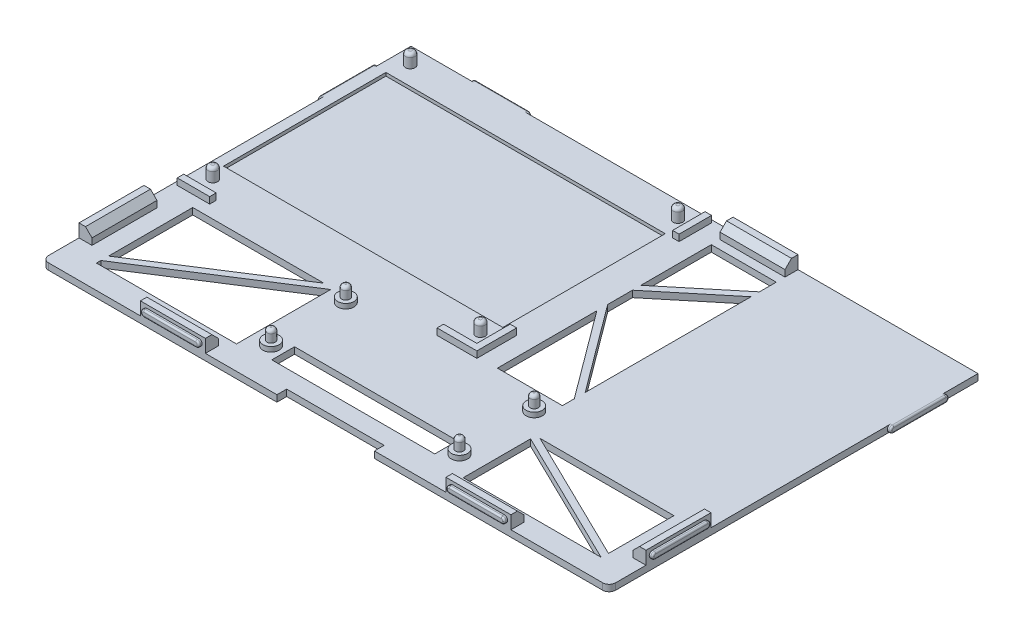
SolidWorks part; units mm, degrees
ref_plane "前基準面" through (0, 0, 0) normal (0, 0, 1) x (1, 0, 0)
ref_plane "上基準面" through (0, 0, 0) normal (0, 1, 0) x (1, 0, 0)
ref_plane "右基準面" through (0, 0, 0) normal (1, 0, 0) x (0, 0, -1)
sketch "草圖1" plane through (0, 0, 0) normal (0, 1, 0) x (1, 0, 0)
  line L0 (0, 56.775) -> (0, -56.775) construction
  line L1 (-87.275, 56.775) -> (87.275, 56.775)
  line L2 (-87.275, 56.775) -> (-87.275, -56.775)
  line L3 (-87.275, -56.775) -> (87.275, -56.775)
  line L4 (87.275, 56.775) -> (87.275, -56.775)
  line L5 (-87.275, 56.775) -> (87.275, -56.775) construction
  line L6 (-87.275, -56.775) -> (87.275, 56.775) construction
  line L7 (-87.275, 0) -> (87.275, 0) construction
  point P0 (0, 0)
  dimension "D1" = 174.55
  dimension "D2" = 113.55
extrude "填料-伸長1" add sketch "草圖1" along normal blind 2
sketch "草圖2" plane through (0, 2, 0) normal (0, 1, 0) x (1, 0, 0)
  line L1 (-86.16, 55.93) -> (3.84, 55.93)
  line L2 (-86.16, 55.93) -> (-86.16, -14.07)
  line L3 (-86.16, -14.07) -> (3.84, -14.07)
  line L4 (3.84, 55.93) -> (3.84, -14.07)
  line L5 (-86.16, 55.93) -> (3.84, -14.07) construction
  line L6 (-86.16, -14.07) -> (3.84, 55.93) construction
  line L8 (-41.16, 55.93) -> (-41.16, -14.07) construction
  line L9 (-86.16, 20.93) -> (3.84, 20.93) construction
  line L10 (0, 56.775) -> (0, -56.775) construction
  line L11 (-87.275, 0) -> (87.275, 0) construction
  point P0 (-41.16, 20.93)
  dimension "D1" = 90
  dimension "D2" = 70
  dimension "D3" = 41.16
  dimension "D4" = 20.93
sketch "草圖3" plane through (0, 2, 0) normal (0, 1, 0) x (1, 0, 0)
  line L0 (3.84, 55.93) -> (3.84, -14.07) construction
  line L1 (4.09, 55.93) -> (6.09, 55.93)
  line L2 (4.09, 55.93) -> (4.09, 45.93)
  line L3 (4.09, 45.93) -> (6.09, 45.93)
  line L4 (6.09, 55.93) -> (6.09, 45.93)
  line L5 (-86.16, -14.07) -> (3.84, -14.07) construction
  line L7 (4.09, -14.07) -> (4.09, -4.07)
  line L8 (4.09, -4.07) -> (6.09, -4.07)
  line L9 (6.09, -14.07) -> (6.09, -4.07)
  line L10 (6.09, -16.32) -> (-6.16, -16.32)
  line L11 (6.09, -16.32) -> (6.09, -15.07)
  line L12 (4.09, -14.32) -> (-6.16, -14.32)
  line L13 (-6.16, -16.32) -> (-6.16, -14.32)
  line L14 (3.84, -14.32) -> (3.84, -16.32) construction
  line L15 (4.09, -14.07) -> (4.09, -14.32)
  line L16 (6.09, -14.07) -> (6.09, -15.07)
  line L18 (-86.16, -16.32) -> (-76.16, -16.32)
  line L19 (-86.16, -16.32) -> (-86.16, -14.32)
  line L20 (-86.16, -14.32) -> (-76.16, -14.32)
  line L21 (-76.16, -16.32) -> (-76.16, -14.32)
  dimension "D1" = 2
  dimension "D2" = 10
  dimension "D3" = 0.25
  dimension "D4" = 2
  dimension "D5" = 2
  dimension "D6" = 2
  dimension "D8" = 0.25
  dimension "D9" = 10
  dimension "D11" = 10
extrude "填料-伸長2" add sketch "草圖3" along normal blind 2
sketch "草圖4" plane through (0, 2, 0) normal (0, 1, 0) x (1, 0, 0)
  line L1 (-86.16, 55.93) -> (3.84, 55.93) construction
  line L2 (3.84, 55.93) -> (3.84, -14.07) construction
  line L3 (-86.16, -14.07) -> (3.84, -14.07) construction
  line L4 (-41.16, 55.93) -> (-41.16, -14.07) construction
  circle A0 centre (0.04, 51.63) radius 1.45
  circle A1 centre (0.04, -9.17) radius 1.45
  circle A2 centre (-82.36, -9.17) radius 1.45
  circle A3 centre (-82.36, 51.63) radius 1.45
  dimension "D1" = 2.9
  dimension "D2" = 3.8
  dimension "D3" = 4.3
  dimension "D4" = 4.9
extrude "填料-伸長3" add sketch "草圖4" along normal blind 4
fillet "圓角2" radius 1 4 edges at (-82.36, 6, -53.08) (-82.36, 6, 7.72) (0.04, 6, 10.62) (0.04, 6, -50.18)
sketch "草圖6" plane through (0, 2, 0) normal (0, 1, 0) x (1, 0, 0)
  line L1 (35.1797, 56.0179) -> (85.1797, 56.0179)
  line L2 (35.1797, 56.0179) -> (35.1797, -24.9821)
  line L3 (35.1797, -24.9821) -> (85.1797, -24.9821)
  line L4 (85.1797, 56.0179) -> (85.1797, -24.9821)
  line L5 (35.1797, 56.0179) -> (85.1797, -24.9821) construction
  line L6 (35.1797, -24.9821) -> (85.1797, 56.0179) construction
  point P0 (60.1797, 15.5179)
  dimension "D1" = 81
  dimension "D2" = 50
sketch "草圖5" plane through (0, 2, 0) normal (0, 1, 0) x (1, 0, 0)
  line L0 (-86.16, 55.93) -> (3.84, -14.07) construction
  line L1 (-84.16, 45.93) -> (1.84, 45.93)
  line L2 (-84.16, 45.93) -> (-84.16, -4.07)
  line L3 (-84.16, -4.07) -> (1.84, -4.07)
  line L4 (1.84, 45.93) -> (1.84, -4.07)
  line L5 (-84.16, 45.93) -> (1.84, -4.07) construction
  line L6 (-84.16, -4.07) -> (1.84, 45.93) construction
  line L7 (-86.16, 55.93) -> (3.84, 55.93) construction
  line L8 (-86.16, 55.93) -> (-86.16, -14.07) construction
  point P0 (-41.16, 20.93)
  dimension "D1" = 10
  dimension "D2" = 2
extrude "除料-伸長1" cut sketch "草圖5" against normal blind 1
sketch "草圖7" plane through (0, 2, 0) normal (0, 1, 0) x (1, 0, 0)
  line L0 (0, 56.775) -> (0, -56.775) construction
  line L1 (-32.5, -18.075) -> (32.5, -18.075)
  line L2 (-32.5, -18.075) -> (-32.5, -48.275)
  line L3 (-32.5, -48.275) -> (32.5, -48.275)
  line L4 (32.5, -18.075) -> (32.5, -48.275)
  line L5 (-32.5, -18.075) -> (32.5, -48.275) construction
  line L6 (-32.5, -48.275) -> (32.5, -18.075) construction
  line L7 (-87.275, -56.775) -> (87.275, -56.775) construction
  point P0 (0, -33.175)
  point P5 (32.5, -33.175)
  dimension "D1" = 65
  dimension "D2" = 30.2
  dimension "D3" = 8.5
sketch "草圖8" plane through (0, 2, 0) normal (0, 1, 0) x (1, 0, 0)
  line L0 (-32.5, -18.075) -> (32.5, -18.075) construction
  line L1 (32.5, -18.075) -> (32.5, -48.275) construction
  line L2 (-32.5, -48.275) -> (32.5, -48.275) construction
  line L3 (0, -18.075) -> (0, -48.275) construction
  circle A0 centre (29, -21.575) radius 2.5
  circle A1 centre (29, -21.575) radius 1.25
  circle A2 centre (29, -44.575) radius 2.5
  circle A3 centre (29, -44.575) radius 1.25
  circle A4 centre (-29, -44.575) radius 1.25
  circle A5 centre (-29, -44.575) radius 2.5
  circle A6 centre (-29, -21.575) radius 1.25
  circle A7 centre (-29, -21.575) radius 2.5
  dimension "D1" = 5
  dimension "D4" = 2.5
  dimension "D2" = 3.5
  dimension "D3" = 3.5
  dimension "D5" = 3.7
extrude "填料-伸長4" add sketch "草圖8" along normal blind 1.5 contours A6 | A7 A6 | A5 A4 | A4 | A0 A1 | A1 | A2 A3 | A3 region at (26.5707, 2, 21.575) region at (29, 2, 21.575) region at (26.5707, 2, 44.575) region at (29, 2, 44.575) region at (-29, 2, 44.575) region at (-31.4293, 2, 44.575) region at (-29, 2, 21.575) region at (-31.4293, 2, 21.575)
extrude "填料-伸長5" add sketch "草圖8<3>" along normal blind 5 contours A6 | A4 | A3 | A1 region at (29, 2, 21.575) region at (29, 2, 44.575) region at (-29, 2, 44.575) region at (-29, 2, 21.575)
sketch "草圖8<3>" plane through (0, 2, 0) normal (0, 1, 0) x (1, 0, 0) same geometry as "草圖8"
fillet "圓角3" radius 1 4 edges at (-29, 7, 45.825) (29, 7, 45.825) (29, 7, 22.825) (-29, 7, 22.825)
sketch "草圖9" plane through (0, 2, 0) normal (0, 1, 0) x (1, 0, 0)
  line L0 (0, 56.775) -> (0, -56.775) construction
  line L1 (-25.0798, -41.275) -> (25.0798, -41.275)
  line L2 (-25.0798, -41.275) -> (-25.0798, -48.275)
  line L3 (-25.0798, -48.275) -> (25.0798, -48.275)
  line L4 (25.0798, -41.275) -> (25.0798, -48.275)
  line L5 (-25.0798, -41.275) -> (25.0798, -48.275) construction
  line L6 (-25.0798, -48.275) -> (25.0798, -41.275) construction
  line L7 (-32.5, -48.275) -> (32.5, -48.275) construction
  line L8 (-87.275, -56.775) -> (87.275, -56.775) construction
  line L9 (-15, -53.775) -> (15, -53.775)
  line L10 (-15, -53.775) -> (-15, -56.775)
  line L11 (-15, -56.775) -> (15, -56.775)
  line L12 (15, -53.775) -> (15, -56.775)
  line L13 (-15, -53.775) -> (15, -56.775) construction
  line L14 (-15, -56.775) -> (15, -53.775) construction
  point P0 (0, -44.775)
  point P9 (0, -55.275)
  dimension "D1" = 7
  dimension "D2" = 3
  dimension "D3" = 30
extrude "除料-伸長2" cut sketch "草圖9" against normal blind 2
sketch "草圖10" plane through (0, 2, 0) normal (0, 1, 0) x (1, 0, 0)
  line L0 (-87.275, 56.775) -> (87.275, 56.775) construction
  line L1 (11.8547, 56.775) -> (31.8547, 56.775)
  line L2 (11.8547, 56.775) -> (11.8547, 52.775)
  line L3 (11.8547, 52.775) -> (31.8547, 52.775)
  line L4 (31.8547, 56.775) -> (31.8547, 52.775)
  line L5 (0, 56.775) -> (0, -56.775) construction
  line L10 (87.275, 56.775) -> (87.275, -56.775) construction
  line L11 (87.275, -25.438) -> (83.275, -25.438)
  line L12 (87.275, -25.438) -> (87.275, -45.438)
  line L13 (87.275, -45.438) -> (83.275, -45.438)
  line L14 (83.275, -25.438) -> (83.275, -45.438)
  line L15 (-87.275, -56.775) -> (87.275, -56.775) construction
  line L16 (37.0319, -56.775) -> (57.0319, -56.775)
  line L17 (37.0319, -56.775) -> (37.0319, -52.775)
  line L18 (37.0319, -52.775) -> (57.0319, -52.775)
  line L19 (57.0319, -56.775) -> (57.0319, -52.775)
  line L20 (-57.0319, -56.775) -> (-57.0319, -52.775)
  line L21 (-37.0319, -52.775) -> (-57.0319, -52.775)
  line L22 (-37.0319, -56.775) -> (-37.0319, -52.775)
  line L23 (-37.0319, -56.775) -> (-57.0319, -56.775)
  line L29 (-83.275, -25.438) -> (-83.275, -45.438)
  line L30 (-87.275, -45.438) -> (-83.275, -45.438)
  line L31 (-87.275, -25.438) -> (-87.275, -45.438)
  line L32 (-87.275, -25.438) -> (-83.275, -25.438)
  dimension "D1" = 4
  dimension "D2" = 20
  dimension "D5" = 20
  dimension "D6" = 4
  dimension "D7" = 20
  dimension "D8" = 4
  dimension "D10" = 82.213
extrude "填料-伸長6" add sketch "草圖10" along normal blind 4
sketch "草圖11" plane through (0, 2, 0) normal (0, 1, 0) x (1, 0, 0)
  line L0 (-77.8796, -45.7226) -> (-37.4971, -19.8239)
  line L1 (-77.8796, -49.4672) -> (-34.7645, -49.4672)
  line L2 (-77.8796, -49.4672) -> (-77.8796, -48.0986)
  line L3 (-77.8796, -19.8239) -> (-37.4971, -19.8239)
  line L4 (-34.7645, -49.4672) -> (-34.7645, -20.4474)
  line L5 (-77.8796, -48.0986) -> (-34.7645, -20.4474)
  line L6 (-77.8796, -45.7226) -> (-77.8796, -19.8239)
  line L7 (31.8547, 44.9175) -> (11.8547, 28.4103)
  line L8 (11.8547, 50.0907) -> (31.8547, 50.0907)
  line L9 (11.8547, 50.0907) -> (11.8547, 28.4103)
  line L10 (11.8547, -15.7529) -> (31.8547, -15.7529)
  line L11 (31.8547, 50.0907) -> (31.8547, 44.9175)
  line L13 (11.8547, 25.8171) -> (31.8547, 42.3243)
  line L14 (11.8547, 18.1985) -> (31.8547, -8.7367)
  line L15 (11.8547, 14.8436) -> (31.8547, -12.0916)
  line L16 (31.8547, 42.3243) -> (31.8547, -8.7367)
  line L17 (11.8547, 25.8171) -> (11.8547, 18.1985)
  line L18 (11.8547, 14.8436) -> (11.8547, -15.7529)
  line L19 (31.8547, -12.0916) -> (31.8547, -15.7529)
  line L20 (78.3594, -48.0628) -> (37.1158, -27.9151)
  line L21 (37.1158, -27.9151) -> (78.3594, -27.9151)
  line L22 (35.8042, -29.5002) -> (35.8042, -50.2291)
  line L23 (35.8042, -50.2291) -> (78.2374, -50.2291)
  line L24 (78.3594, -27.9151) -> (78.3594, -48.0628)
  line L25 (35.8042, -29.5002) -> (78.2374, -50.2291)
  dimension "D1" = 2
  dimension "D2" = 2
  dimension "D3" = 2
  dimension "D4" = 2
extrude "除料-伸長3" cut sketch "草圖11" against normal through all
fillet "圓角1" radius 2 2 edges at (-87.275, 1, 56.775) (87.275, 1, 56.775)
chamfer "導角1" distance 2 angle 45 5 edges at (83.275, 6, 35.438) (47.0319, 6, 52.775) (-47.0319, 6, 52.775) (21.8547, 6, -52.775) (-83.275, 6, 35.438)
sketch "草圖13" plane through (87.275, 0, 0) normal (1, 0, 0) x (0, 0, -1)
  line L0 (-43.438, 4) -> (-27.438, 4) construction
  line L1 (-43.438, 5) -> (-27.438, 5)
  line L2 (-43.438, 3) -> (-27.438, 3)
  line L4 (-45.438, 4) -> (-25.438, 4) construction
  line L5 (-45.438, 6) -> (-45.438, 2) construction
  arc A0 (-43.438, 5) -> (-43.438, 3) centre (-43.438, 4) ccw
  arc A1 (-27.438, 3) -> (-27.438, 5) centre (-27.438, 4) ccw
  point P2 (-35.438, 4)
  point P16 (-35.438, 4)
  dimension "D1" = 2
  dimension "D2" = 16
extrude "填料-伸長8" add sketch "草圖13" along normal blind 1
sketch "草圖14" plane through (0, 0, -56.775) normal (0, 0, -1) x (-1, 0, 0)
  line L0 (-31.8547, 4) -> (-11.8547, 4) construction
  line L1 (-31.8547, 6) -> (-31.8547, 2) construction
  line L2 (-29.8547, 4) -> (-13.8547, 4) construction
  line L3 (-29.8547, 5) -> (-13.8547, 5)
  line L4 (-29.8547, 3) -> (-13.8547, 3)
  arc A0 (-29.8547, 5) -> (-29.8547, 3) centre (-29.8547, 4) ccw
  arc A1 (-13.8547, 3) -> (-13.8547, 5) centre (-13.8547, 4) ccw
  point P7 (-21.8547, 4)
  point P13 (-21.8547, 4)
  dimension "D1" = 16
  dimension "D2" = 2
extrude "填料-伸長9" add sketch "草圖14" along normal blind 1
sketch "草圖15" plane through (0, 0, 56.775) normal (0, 0, 1) x (1, 0, 0)
  line L0 (-57.0319, 4) -> (-37.0319, 4) construction
  line L1 (-57.0319, 6) -> (-57.0319, 2) construction
  line L2 (-37.0319, 6) -> (-37.0319, 2) construction
  line L3 (-55.0319, 4) -> (-39.0319, 4) construction
  line L4 (-55.0319, 5) -> (-39.0319, 5)
  line L5 (-55.0319, 3) -> (-39.0319, 3)
  line L6 (0, 2) -> (0, 0) construction
  line L7 (55.0319, 4) -> (39.0319, 4) construction
  line L8 (55.0319, 5) -> (39.0319, 5)
  line L9 (55.0319, 3) -> (39.0319, 3)
  arc A0 (-55.0319, 5) -> (-55.0319, 3) centre (-55.0319, 4) ccw
  arc A1 (-39.0319, 3) -> (-39.0319, 5) centre (-39.0319, 4) ccw
  arc A2 (55.0319, 5) -> (55.0319, 3) centre (55.0319, 4) cw
  arc A3 (39.0319, 3) -> (39.0319, 5) centre (39.0319, 4) cw
  point P8 (-47.0319, 4)
  point P16 (47.0319, 4)
  dimension "D1" = 16
  dimension "D2" = 2
extrude "填料-伸長11" add sketch "草圖15" along normal blind 1
sketch "草圖16" plane through (-87.275, 0, 0) normal (-1, 0, 0) x (0, 0, 1)
  line L0 (25.438, 6) -> (45.438, 6) construction
  line L3 (27.438, 4) -> (43.438, 4) construction
  line L4 (27.438, 5) -> (43.438, 5)
  line L5 (27.438, 3) -> (43.438, 3)
  arc A0 (27.438, 5) -> (27.438, 3) centre (27.438, 4) ccw
  arc A1 (43.438, 3) -> (43.438, 5) centre (43.438, 4) ccw
  point P0 (0, 0)
  point P3 (35.438, 6)
  point P8 (35.438, 4)
  point P16 (47.4, 4)
  point P17 (47.4, 4)
  dimension "D1" = 16
  dimension "D2" = 2
extrude "填料-伸長12" add sketch "草圖16" along normal blind 1
ref_plane "Plane7" through (0, 0, 0) normal (-1, 0, 0) x (0, 0, 1)
sketch "Sketch1" plane through (0, 0, -56.775) normal (0, 0, -1) x (-1, 0, 0)
  line L0 (68.15, 1) -> (52.15, 1) construction
  line L1 (68.15, 0) -> (52.15, 0)
  line L2 (68.15, 2) -> (52.15, 2)
  line L3 (87.275, 2) -> (87.275, 0) construction
  arc A0 (68.15, 0) -> (68.15, 2) centre (68.15, 1) ccw
  arc A1 (52.15, 2) -> (52.15, 0) centre (52.15, 1) ccw
  point P2 (60.15, 1)
  point P7 (87.275, 1)
  dimension "D1" = 16
  dimension "D2" = 2
  dimension "D3" = 60.15
extrude "Boss-Extrude1" add sketch "Sketch1" along normal blind 1
sketch "Sketch2" plane through (87.275, 0, 0) normal (1, 0, 0) x (0, 0, -1)
  line L0 (29.84, 1) -> (45.84, 1) construction
  line L1 (29.84, 2) -> (45.84, 2)
  line L2 (29.84, 0) -> (45.84, 0)
  line L3 (56.775, 0) -> (56.775, 2) construction
  arc A0 (29.84, 2) -> (29.84, 0) centre (29.84, 1) ccw
  arc A1 (45.84, 0) -> (45.84, 2) centre (45.84, 1) ccw
  point P2 (37.84, 1)
  point P7 (56.775, 1)
  dimension "D1" = 16
  dimension "D2" = 2
  dimension "D3" = 37.84
extrude "Boss-Extrude2" add sketch "Sketch2" along normal blind 1
mirror "Mirror1" about plane through (0, 0, 0) normal (-1, 0, 0) of "Boss-Extrude2"
fillet "圓角4" radius 0.5 32 edges at (12.8547, 4, -57.775) (21.8547, 3, -57.775) (30.8547, 4, -57.775) (88.275, 4, 26.438) (88.275, 3, 35.438) (88.275, 4, 44.438) (56.0319, 4, 57.775) (47.0319, 3, 57.775) (38.0319, 4, 57.775) (-88.275, 4, 44.438) (-88.275, 3, 35.438) (-88.275, 4, 26.438) (-38.0319, 4, 57.775) (-47.0319, 3, 57.775) (-56.0319, 4, 57.775) (21.8547, 5, -57.775) (88.275, 5, 35.438) (47.0319, 5, 57.775) (-88.275, 5, 35.438) (-47.0319, 5, 57.775) (-88.275, 1, -46.84) (-88.275, 0, -37.84) (-88.275, 1, -28.84) (88.275, 1, -46.84) (88.275, 0, -37.84) (88.275, 1, -28.84) (-69.15, 1, -57.775) (-60.15, 0, -57.775) (-51.15, 1, -57.775) (-88.275, 2, -37.84) (88.275, 2, -37.84) (-60.15, 2, -57.775)
